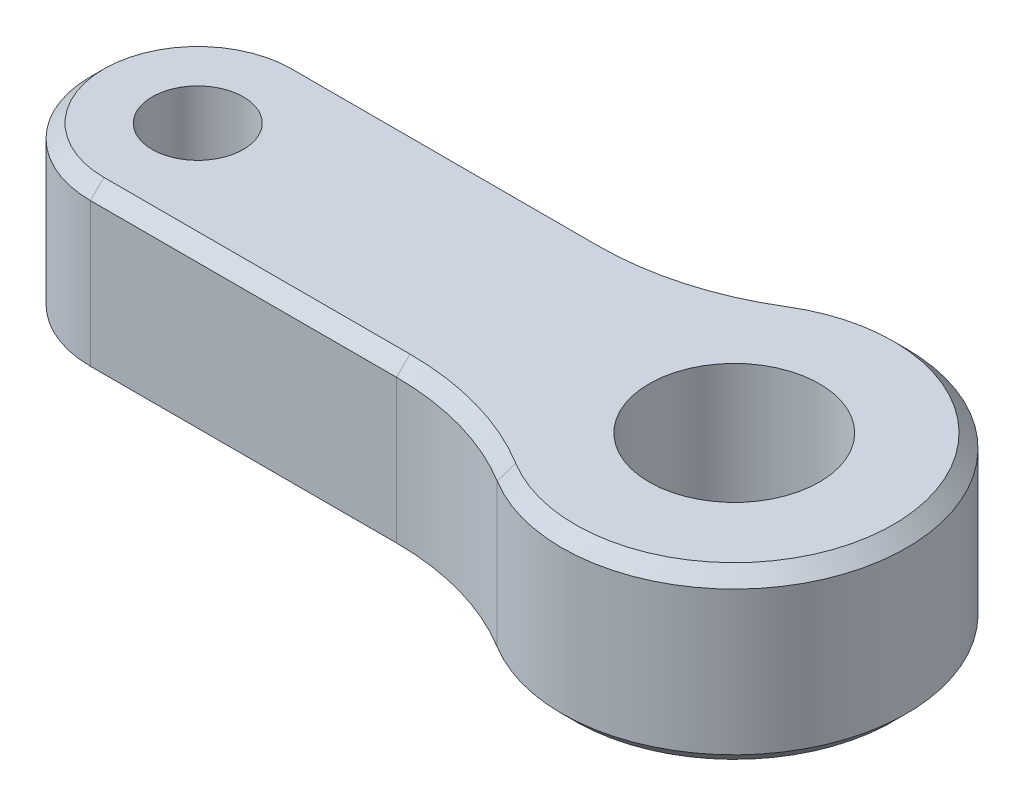
SolidWorks part; units mm, degrees
ref_plane "Front Plane" through (0, 0, 0) normal (0, 0, 1) x (1, 0, 0)
ref_plane "Top Plane" through (0, 0, 0) normal (0, 1, 0) x (1, 0, 0)
ref_plane "Right Plane" through (0, 0, 0) normal (1, 0, 0) x (0, 0, -1)
sketch "Sketch2" plane through (0, 0, 0) normal (0, 1, 0) x (1, 0, 0)
  line L0 (0, 0) -> (20, 0) construction
  line L1 (0, 4) -> (20, 4)
  line L2 (0, -4) -> (20, -4)
  arc A0 (0, 4) -> (0, -4) centre (0, 0) ccw
  arc A1 (20, -4) -> (20, 4) centre (20, 0) ccw
  circle A2 centre (0, 0) radius 1.7
  circle A3 centre (20, 0) radius 3.175
  circle A4 centre (20, 0) radius 6.425
  point P3 (10, 0)
  dimension "D2" = 3.4
  dimension "D4" = 6.35
  dimension "D5" = 12.85
  dimension "D1" = 20
  dimension "D3" = 8
extrude "Boss-Extrude1" add sketch "Sketch2" along normal blind 6.35 contours A2 A4 L1 A0 L2 | L1 A4 A3 L2 A1 | L2 A4 L1 A1 region at (5.8039, 0, 0) region at (22.0617, 0, -5.9032) region at (17.486, 0, -3.8686)
fillet "Fillet1" radius 10 2 edges at (14.972, 3.175, 4) (14.972, 3.175, -4)
chamfer "Chamfer2" distance 0.5 angle 45 12 edges at (14.1274, 0, 4.3762) (5.7052, 0, 4) (26.425, 0, 0) (-4, 0, 0) (14.1274, 0, -4.3762) (5.7052, 0, -4) (14.1274, 6.35, 4.3762) (5.7052, 6.35, 4) (26.425, 6.35, 0) (-4, 6.35, 0) (14.1274, 6.35, -4.3762) (5.7052, 6.35, -4)
ref_point "Point1"
equation "\"D5@Sketch2\"=\"D4@Sketch2\"+6.5mm"
